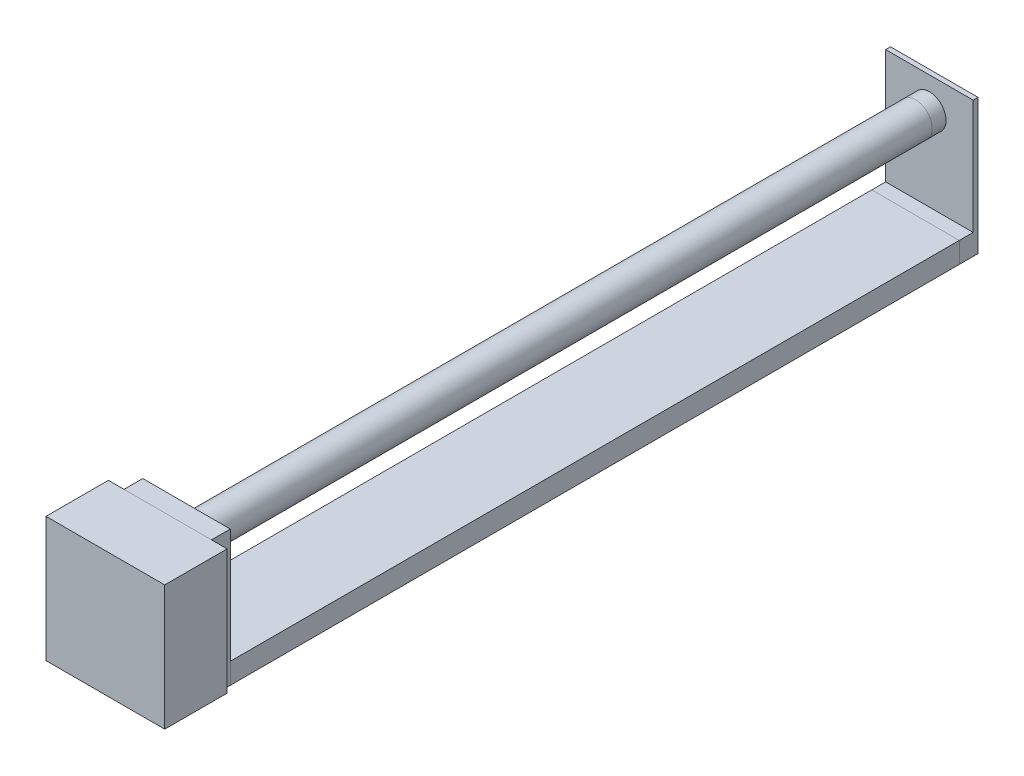
SolidWorks part; units mm, degrees
ref_plane "前视基准面" through (0, 0, 0) normal (0, 0, 1) x (1, 0, 0)
ref_plane "上视基准面" through (0, 0, 0) normal (0, 1, 0) x (1, 0, 0)
ref_plane "右视基准面" through (0, 0, 0) normal (1, 0, 0) x (0, 0, -1)
sketch "草图1" plane through (0, 0, 0) normal (0, 0, 1) x (1, 0, 0)
  line L1 (21, -5) -> (-21, -5)
  line L2 (21, -5) -> (21, 5)
  line L3 (21, 5) -> (-21, 5)
  line L4 (-21, -5) -> (-21, 5)
  line L5 (21, -5) -> (-21, 5) construction
  line L6 (21, 5) -> (-21, -5) construction
  point P0 (0, 0)
  dimension "D1" = 42
  dimension "D2" = 10
extrude "凸台-拉伸1" add sketch "草图1" along normal blind 350
sketch "草图2" plane through (0, 0, 0) normal (0, 0, -1) x (-1, 0, 0)
  line L0 (21, 5) -> (21, -5) construction
  line L1 (-21, -5) -> (21, -5)
  line L2 (-21, -5) -> (-21, 60)
  line L3 (-21, 60) -> (21, 60)
  line L4 (21, -5) -> (21, 60)
  dimension "D1" = 65
extrude "凸台-拉伸2" add sketch "草图2" along normal blind 9 separate body
sketch "草图3" plane through (0, 0, 350) normal (0, 0, 1) x (1, 0, 0)
  line L1 (-21, -5) -> (21, -5)
  line L2 (-21, -5) -> (-21, 60)
  line L3 (-21, 60) -> (21, 60)
  line L4 (21, -5) -> (21, 60)
extrude "凸台-拉伸3" add sketch "草图3" along normal blind 9 separate body contours L3 L4 L1 L2
sketch "草图4" plane through (0, 0, 0) normal (0, 0, 1) x (1, 0, 0)
  line L0 (0, 60) -> (0, -5) construction
  line L1 (-21, 60) -> (21, 60) construction
  line L2 (-21, -5) -> (21, -5) construction
  circle A0 centre (0, 45) radius 8
  dimension "D1" = 16
  dimension "D2" = 15
extrude "凸台-拉伸4" add sketch "草图4" along normal up to surface (350 mm away) separate body up to face at (0, 27.5, 350)
sketch "草图5" plane through (0, 0, 359) normal (0, 0, 1) x (1, 0, 0)
  line L1 (0, 0) -> (0, 60) construction
  line L2 (-28.5, 60) -> (28.5, 60)
  line L3 (-28.5, 60) -> (-28.5, 0)
  line L4 (-28.5, 0) -> (28.5, 0)
  line L6 (28.5, 60) -> (28.5, 0)
  line L7 (-21, 60) -> (21, 60) construction
  dimension "D1" = 57
  dimension "D2" = 60
extrude "凸台-拉伸5" add sketch "草图5" along normal blind 56 separate body
scale "缩放比例1" bodies to scale 106 109 110 107 108 scale about origin uniform scaling yes scale factor 0.3
sketch "草图6" plane through (0, 0, 0) normal (0, 0, 1) x (1, 0, 0)
  line L1 (-6.3, 18) -> (6.3, 18)
  line L2 (-6.3, 18) -> (-6.3, 1.5)
  line L3 (-6.3, 1.5) -> (6.3, 1.5)
  line L4 (6.3, 18) -> (6.3, 1.5)
  circle A0 centre (0, 13.5) radius 2.4 construction
  circle A1 centre (0, 13.5) radius 2.4
extrude "切除-拉伸1" cut sketch "草图6" against normal blind 2
sketch "草图7" plane through (0, 18, 0) normal (0, 1, 0) x (1, 0, 0)
  line L1 (-19.1662, -116.6888) -> (23.3053, -116.6888)
  line L2 (-19.1662, -116.6888) -> (-19.1662, -133.2455)
  line L3 (-19.1662, -133.2455) -> (23.3053, -133.2455)
  line L4 (23.3053, -116.6888) -> (23.3053, -133.2455)
extrude "切除-拉伸2" cut sketch "草图7" against normal blind 30
